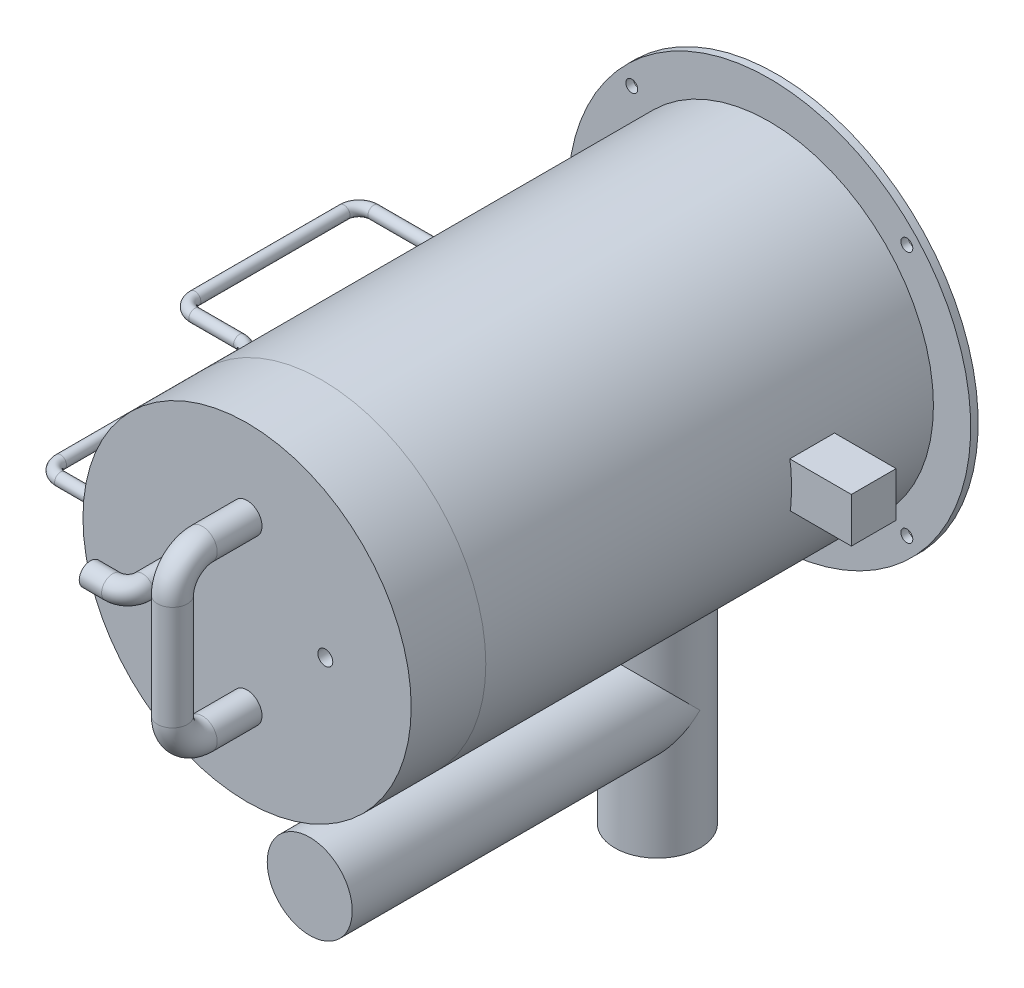
SolidWorks part; units mm, degrees
ref_plane "前视基准面" through (0, 0, 0) normal (0, 0, 1) x (1, 0, 0)
ref_plane "上视基准面" through (0, 0, 0) normal (0, 1, 0) x (1, 0, 0)
ref_plane "右视基准面" through (0, 0, 0) normal (1, 0, 0) x (0, 0, -1)
sketch "草图1" plane through (0, 0, 0) normal (0, 0, 1) x (1, 0, 0)
  circle A0 centre (0, 0) radius 110
  dimension "D1" = 220
extrude "凸台-拉伸1" add sketch "草图1" along normal blind 50
sketch "草图2" plane through (0, 0, 50) normal (0, 0, 1) x (1, 0, 0)
  circle A0 centre (0, 0) radius 110
  circle A1 centre (0, 0) radius 90
  dimension "D1" = 180
  dimension "D2" = 220
extrude "凸台-拉伸2" add sketch "草图2" along normal blind 250
sketch "草图4" plane through (0, 0, 0) normal (0, 1, 0) x (1, 0, 0)
  line L0 (110, 0) -> (-110, 0) construction
  circle A0 centre (0, -75) radius 28.5
  dimension "D1" = 57
  dimension "D2" = 75
extrude "凸台-拉伸7" add sketch "草图4" against normal blind 260 separate body
sketch "草图5" plane through (0, 0, 0) normal (0, 1, 0) x (-1, 0, 0)
  circle A0 centre (0, 75) radius 28.5
  dimension "D1" = 57
sketch "草图7" plane through (0, 0, 0) normal (0, 0, -1) x (-1, 0, 0)
  circle A0 centre (0, 0) radius 135
  dimension "D1" = 270
extrude "凸台-拉伸9" add sketch "草图7" along normal blind 5
sketch "草图8" plane through (0, 0, 300) normal (0, 0, 1) x (1, 0, 0)
  circle A0 centre (0, 0) radius 110
  dimension "D1" = 220
extrude "凸台-拉伸10" add sketch "草图8" along normal blind 50 separate body
sketch "草图9" plane through (0, 0, 0) normal (0, 0, 1) x (1, 0, 0)
  circle A0 centre (0, 0) radius 125 construction
  circle A1 centre (92.1659, 84.442) radius 4
  circle A2 centre (92.1659, -84.442) radius 4
  circle A3 centre (-92.1659, -84.442) radius 4
  circle A4 centre (-92.1659, 84.442) radius 4
  dimension "D1" = 250
  dimension "D2" = 8
  dimension "D3" = 8
  dimension "D4" = 8
  dimension "D5" = 8
extrude "切除-拉伸1" cut sketch "草图9" against normal blind 20
sketch "草图10" plane through (0, 0, 0) normal (1, 0, 0) x (0, 0, -1)
  line L0 (0, 135) -> (0, -135) construction
  line L1 (-95, -14.0115) -> (-65, -14.0115)
  line L2 (-95, -14.0115) -> (-95, 15.9885)
  line L3 (-95, 15.9885) -> (-65, 15.9885)
  line L4 (-65, -14.0115) -> (-65, 15.9885)
  line L5 (-95, -14.0115) -> (-65, 15.9885) construction
  line L6 (-95, 15.9885) -> (-65, -14.0115) construction
  point P0 (-80, 0.9885)
  dimension "D1" = 30
  dimension "D2" = 30
  dimension "D3" = 80
extrude "凸台-拉伸12" add sketch "草图10" along normal blind 150 separate body
sketch "草图11" plane through (0, 0, 0) normal (1, 0, 0) x (0, 0, -1)
  line L0 (-350, 55) -> (-380, 55)
  line L1 (-350, 110) -> (-350, -110) construction
  line L2 (-400, 35) -> (-400, -35)
  line L3 (-380, -55) -> (-350, -55)
  arc A0 (-380, -55) -> (-400, -35) centre (-380, -35) cw
  arc A1 (-400, 35) -> (-380, 55) centre (-380, 35) cw
  point P5 (-400, 0)
  point P10 (-400, -55)
  point P13 (-400, 55)
  dimension "D4" = 20
  dimension "D1" = 50
  dimension "D2" = 110
  dimension "D3" = 0
sketch "草图12" plane through (0, 0, 350) normal (0, 0, 1) x (1, 0, 0)
  circle A0 centre (0, 55) radius 10
  dimension "D1" = 20
sweep "扫描1" add profiles "草图12" path "草图11"
sketch "草图13" plane through (0, 0, 0) normal (0, 1, 0) x (1, 0, 0)
  line L0 (-50, -350) -> (-50, -370)
  line L1 (-110, -350) -> (110, -350) construction
  line L2 (-60, -380) -> (-75, -380)
  arc A1 (-50, -370) -> (-60, -380) centre (-60, -370) cw
  point P8 (-50, -380)
  dimension "D5" = 10
  dimension "D1" = 30
  dimension "D2" = 25
  dimension "D3" = 60
sketch "草图14" plane through (0, 0, 350) normal (0, 0, 1) x (1, 0, 0)
  circle A0 centre (-50, 0) radius 7.5
  dimension "D1" = 15
sweep "扫描2" add profiles "草图14" path "草图13"
sketch "草图15" plane through (0, 0, 350) normal (0, 0, 1) x (1, 0, 0)
  circle A0 centre (52.432, 0) radius 5
  dimension "D1" = 10
extrude "切除-拉伸2" cut sketch "草图15" against normal blind 125
sketch "草图16" plane through (0, -260, 0) normal (0, -1, 0) x (-1, 0, 0)
  circle A0 centre (0, -75) radius 5
extrude "切除-拉伸3" cut sketch "草图16" against normal blind 125
sketch "草图17" plane through (0, 0, 0) normal (0, 1, 0) x (1, 0, 0)
  line L0 (0, -75) -> (-190, -75)
  line L1 (-200, -85) -> (-200, -185)
  line L2 (-190, -195) -> (-160, -195)
  line L3 (-150, -205) -> (-150, -325)
  line L4 (-140, -335) -> (0, -335)
  arc A0 (-150, -325) -> (-140, -335) centre (-140, -325) ccw
  arc A1 (-160, -195) -> (-150, -205) centre (-160, -205) cw
  arc A2 (-200, -185) -> (-190, -195) centre (-190, -185) ccw
  arc A3 (-190, -75) -> (-200, -85) centre (-190, -85) ccw
  point P9 (-150, -335)
  point P12 (-150, -195)
  point P15 (-200, -195)
  point P18 (-200, -75)
  dimension "D6" = 10
  dimension "D1" = 200
  dimension "D2" = 120
  dimension "D3" = 50
  dimension "D4" = 140
  dimension "D5" = 150
sketch "草图18" plane through (0, 0, 0) normal (1, 0, 0) x (0, 0, -1)
  circle A0 centre (-75, 0) radius 4
  dimension "D1" = 8
sweep "扫描4" add profiles "草图18" path "草图17"
ref_axis "基准轴1" through (0, -135, 75) along (0, -1, 0)
ref_plane "基准面1" through (0, 0, 75) normal (0, 0, -1) x (-1, 0, 0)
sketch "草图19" plane through (0, 0, 75) normal (0, 0, -1) x (-1, 0, 0)
  line L0 (0, -135) -> (0, -260) construction
  circle A0 centre (0, -180) radius 28.5
  dimension "D1" = 180
extrude "凸台-拉伸13" add sketch "草图19" against normal blind 233
